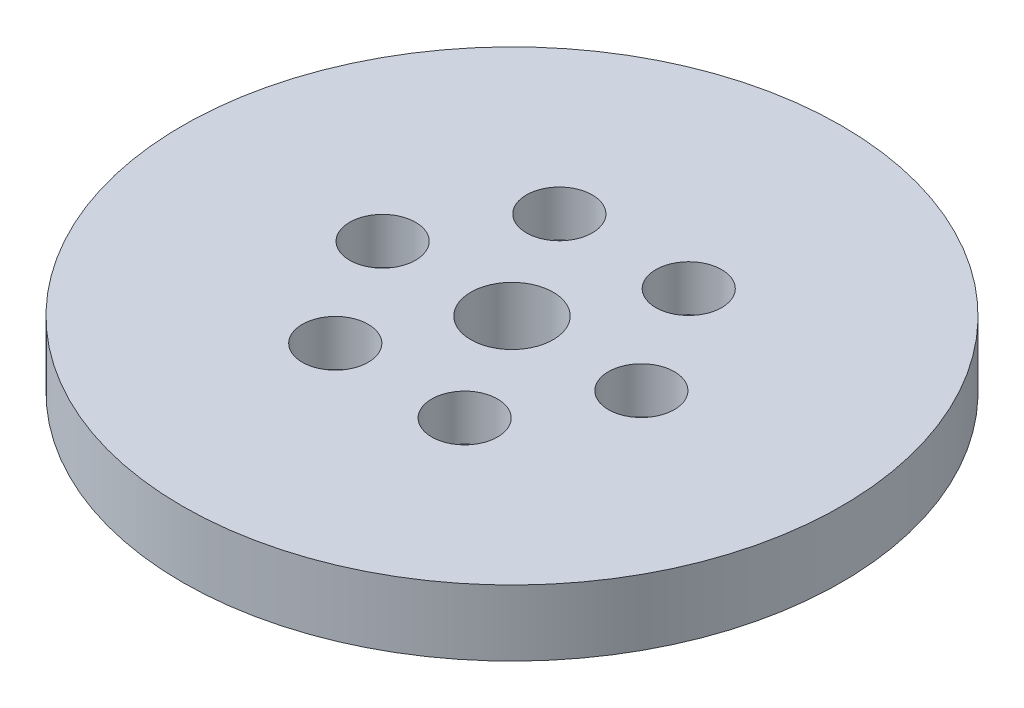
SolidWorks part; units mm, degrees
ref_plane "Front Plane" through (0, 0, 0) normal (0, 0, 1) x (1, 0, 0)
ref_plane "Top Plane" through (0, 0, 0) normal (0, 1, 0) x (1, 0, 0)
ref_plane "Right Plane" through (0, 0, 0) normal (1, 0, 0) x (0, 0, -1)
sketch "Sketch1" plane through (0, 0, 0) normal (0, 1, 0) x (1, 0, 0)
  circle A0 centre (0, 0) radius 100
  dimension "FLANGE_OD" = 200
extrude "Boss-Extrude1" add sketch "Sketch1" along normal blind 20
sketch "Sketch2" plane through (0, 0, 0) normal (0, 1, 0) x (1, 0, 0)
  circle A0 centre (0, 0) radius 12.5
  dimension "BORE_D" = 25
extrude "Cut-Extrude1" cut sketch "Sketch2" along normal through all
sketch "Sketch3" plane through (0, 20, 0) normal (0, 1, 0) x (1, 0, 0)
  circle A0 centre (0, 0) radius 39.2599 construction
  circle A1 centre (-39.2599, 0) radius 10
  dimension "BOLT_D" = 20
  dimension "BOLT_PCD" = 78.5197
extrude "Cut-Extrude2" cut sketch "Sketch3" against normal blind 13.9241
pattern_circular "CirPattern1" count 6 over 360 about axis through (0, 0, 0) along (0, 1, 0) of "Cut-Extrude2"
